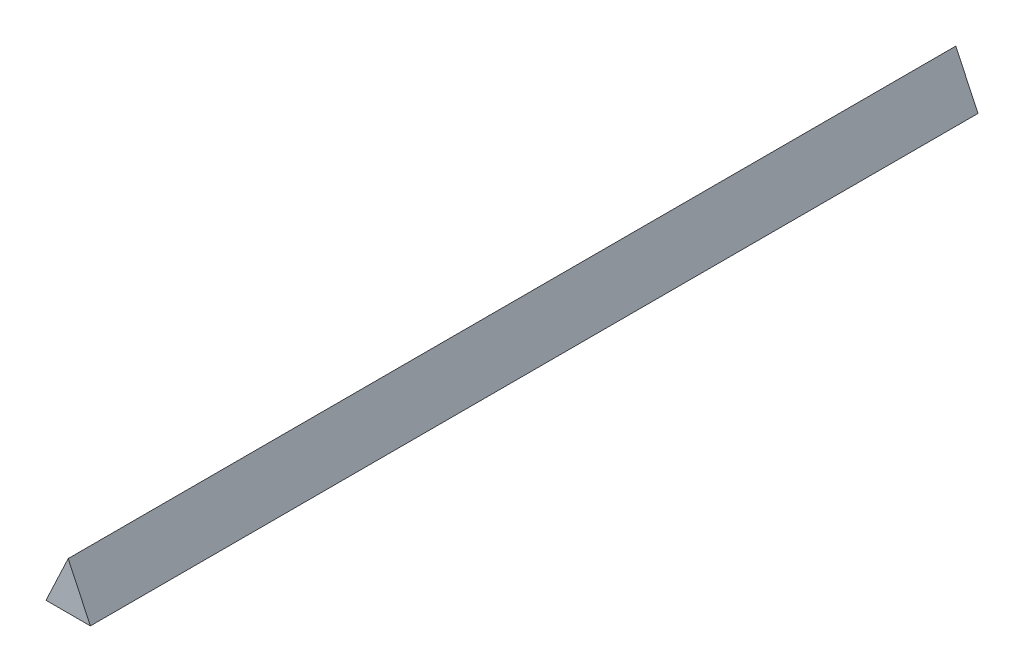
SolidWorks part; units mm, degrees
ref_plane "Спереди" through (0, 0, 0) normal (0, 0, 1) x (1, 0, 0)
ref_plane "Сверху" through (0, 0, 0) normal (0, 1, 0) x (1, 0, 0)
ref_plane "Справа" through (0, 0, 0) normal (1, 0, 0) x (0, 0, -1)
sketch "Эскиз1" plane through (0, 0, 0) normal (0, 0, 1) x (1, 0, 0)
  line L3 (-0.85, 0) -> (0.85, 0)
  line L4 (0.85, 0) -> (0, 1.8104)
  line L5 (0, 1.8104) -> (-0.85, 0)
  dimension "D1" = 1.7
  dimension "D2" = 2
extrude "Бобышка-Вытянуть1" add sketch "Эскиз1" along normal blind 34
